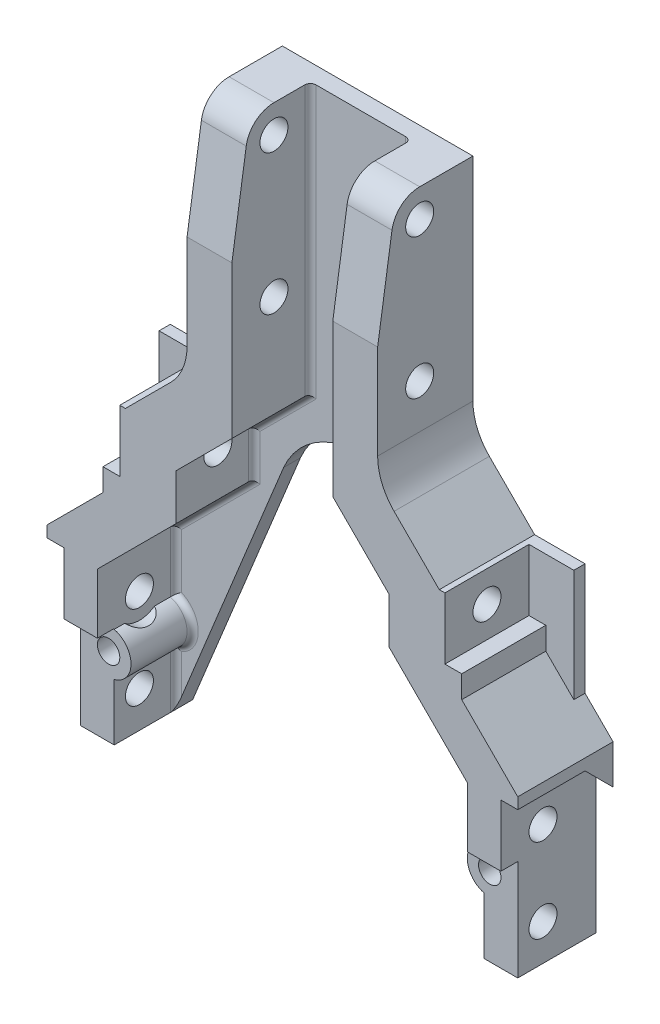
SolidWorks part; units mm, degrees
material "ABS"
ref_plane "Front Plane" through (0, 0, 0) normal (0, 0, 1) x (1, 0, 0)
ref_plane "Top Plane" through (0, 0, 0) normal (0, 1, 0) x (1, 0, 0)
ref_plane "Right Plane" through (0, 0, 0) normal (1, 0, 0) x (0, 0, -1)
sketch "Sketch1" plane through (0, 0, 0) normal (0, 0, 1) x (1, 0, 0)
  line L0 (17, 54.5) -> (17, 12.5)
  line L1 (28, 1.5) -> (17, 12.5)
  line L2 (42, -25.5) -> (39, -25.5)
  line L3 (-42, -25.5) -> (-39, -25.5)
  line L7 (39, -54.5) -> (33, -54.5)
  line L9 (17, 54.5) -> (9, 54.5)
  line L12 (13.7781, -7.5139) -> (33, -54.5)
  line L18 (42, -23.5) -> (37, -18.5)
  line L19 (42, -25.5) -> (42, -23.5)
  line L29 (0, 54.5) -> (9, 54.5)
  line L33 (28, 1.5) -> (29, 1.5)
  line L35 (39, -25.5) -> (39, -54.5)
  line L38 (37, 1.5) -> (37, -18.5)
  line L39 (29, 1.5) -> (37, 1.5)
  line L46 (-28, 1.5) -> (-17, 12.5)
  line L48 (-17, 54.5) -> (-17, 12.5)
  line L53 (-17, 54.5) -> (-9, 54.5)
  line L56 (-42, -23.5) -> (-37, -18.5)
  line L58 (-39, -25.5) -> (-39, -54.5)
  line L63 (-37, 1.5) -> (-37, -18.5)
  line L66 (-28, 1.5) -> (-29, 1.5)
  line L69 (-13.7781, -7.5139) -> (-33, -54.5)
  line L75 (-29, 1.5) -> (-37, 1.5)
  line L76 (-39, -54.5) -> (-33, -54.5)
  line L77 (-42, -25.5) -> (-42, -23.5)
  line L78 (0, 54.5) -> (-9, 54.5)
  arc A0 (13.7781, -7.5139) -> (0, 1.5563) centre (0, -13.4437) ccw
  arc A3 (0, 1.5563) -> (-13.7781, -7.5139) centre (0, -13.4437) ccw
extrude "Boss-Extrude1" add sketch "Sketch1" along normal blind 3
sketch "Sketch2" plane through (0, 0, 3) normal (0, 0, 1) x (1, 0, 0)
  line L0 (-17, 54.5) -> (17, 54.5) construction
  line L1 (17, 54.5) -> (17, 12.5)
  line L2 (28, 1.5) -> (17, 12.5)
  line L3 (33, -30.4706) -> (33, -36.627)
  line L8 (39, -54.5) -> (33, -54.5)
  line L9 (32, -9.5) -> (32, -13.5)
  line L10 (17, 54.5) -> (9, 54.5)
  line L16 (19.0015, -3.6436) -> (9, 6.3579)
  line L17 (9, 54.5) -> (9, 6.3579)
  line L18 (33, -25.8137) -> (19, -11.8137)
  line L19 (42, -23.5) -> (32, -13.5)
  line L20 (42, -25.5) -> (42, -23.5)
  line L22 (33, -30.4706) -> (33, -25.8137)
  line L27 (19, -3.6421) -> (19, -11.8137)
  line L28 (29, -9.5) -> (32, -9.5)
  line L29 (39, -25.5) -> (42, -25.5)
  line L32 (33, -44.373) -> (33, -54.5)
  line L33 (29, -9.5) -> (29, 1.5)
  line L34 (28, 1.5) -> (29, 1.5)
  line L35 (32, -9.5) -> (32, -13.5)
  line L36 (39, -25.5) -> (39, -54.5)
  line L45 (-19.0015, -3.6436) -> (-19.0015, -1.5) construction
  line L47 (-28, 1.5) -> (-17, 12.5)
  line L49 (-17, 54.5) -> (-17, 12.5)
  line L50 (-19, -3.6421) -> (-19, -11.8137)
  line L52 (-19.0015, -1.5) -> (-19.0006, -1.5) construction
  line L53 (-33, -30.4706) -> (-33, -36.627)
  line L54 (-17, 54.5) -> (-9, 54.5)
  line L57 (-42, -23.5) -> (-32, -13.5)
  line L59 (-39, -25.5) -> (-39, -54.5)
  line L60 (-33, -25.8137) -> (-19, -11.8137)
  line L61 (-9, 54.5) -> (-9, 6.3579)
  line L63 (-29, -9.5) -> (-32, -9.5)
  line L66 (-32, -9.5) -> (-32, -13.5)
  line L67 (-28, 1.5) -> (-29, 1.5)
  line L69 (-19.0015, -3.6436) -> (-9, 6.3579)
  line L71 (-29, -9.5) -> (-29, 1.5)
  line L73 (-33, -44.373) -> (-33, -54.5)
  line L74 (-32, -9.5) -> (-32, -13.5)
  line L75 (-39, -25.5) -> (-42, -25.5)
  line L77 (-39, -54.5) -> (-33, -54.5)
  line L78 (-42, -25.5) -> (-42, -23.5)
  line L80 (-33, -30.4706) -> (-33, -25.8137)
  circle A1 centre (34, -40.5) radius 2
  arc A2 (33, -36.627) -> (33, -44.373) centre (34, -40.5) ccw
  circle A4 centre (-34, -40.5) radius 2
  arc A5 (-33, -44.373) -> (-33, -36.627) centre (-34, -40.5) ccw
  line M3 (33, -54.5) -> (39, -54.5)
  line M4 (39, -54.5) -> (39, -25.5)
  line M7 (42, -23.5) -> (37, -18.5)
  line M9 (37, 1.5) -> (28, 1.5)
  line M10 (28, 1.5) -> (17, 12.5)
  line M11 (17, 12.5) -> (17, 54.5)
  line M12 (17, 54.5) -> (-17, 54.5)
  line M13 (-17, 54.5) -> (-17, 12.5)
  line M14 (-17, 12.5) -> (-28, 1.5)
  line M15 (-28, 1.5) -> (-37, 1.5)
  line M17 (-37, -18.5) -> (-42, -23.5)
  line M18 (-42, -23.5) -> (-42, -25.5)
  line M20 (-39, -25.5) -> (-39, -54.5)
  line M21 (-39, -54.5) -> (-33, -54.5)
extrude "Boss-Extrude2" add sketch "Sketch2" along normal blind 14 contours L73 A5 L53 L80 L60 L50 L69 L61 L71 L63 L66 L57 L75 L59 A4 M12 M13 M14 M15 M17 M18 M20 M21 | L3 A2 L32 L36 L29 L19 L9 L28 L33 L17 L16 L27 L18 L22 A1 M3 M4 M7 M9 M10 M11 M12 region at (-22.4143, 1.437, 3) region at (22.4143, 1.437, 3)
sketch "Szkic1" plane through (39, 0, 0) normal (1, 0, 0) x (0, 0, -1)
  line L0 (-17, -54.5) -> (-17, -25.5) construction
  line L1 (-17, -54.5) -> (0, -54.5) construction
  line L2 (-17, -54.5) -> (-14, -54.5)
  line L3 (-17, -54.5) -> (-17, -36.5)
  line L4 (-17, -36.5) -> (-14, -36.5)
  line L5 (-14, -54.5) -> (-14, -36.5)
  line L6 (-17, 33.5) -> (-14.4428, 50.2544)
  line L7 (-17, 12.5) -> (-17, 54.5) construction
  line L9 (-9.5, 54.5) -> (-17, 54.5)
  line L10 (-17, 54.5) -> (-17, 33.5)
  circle A0 centre (-9.5, -48) radius 2.5
  circle A1 centre (-9.5, -33) radius 2.5
  circle A2 centre (-9.5, -4) radius 2.5
  circle A3 centre (-9.5, 24.5) radius 2.5
  circle A4 centre (-9.5, 49.5) radius 2.5
  arc A5 (-9.5, 54.5) -> (-14.4428, 50.2544) centre (-9.5, 49.5) ccw
  dimension "D1" = 7.5
  dimension "D5" = 21.5
  dimension "D6" = 50.5
  dimension "D7" = 79
  dimension "D2" = 18
  dimension "D3" = 3
  dimension "D4" = 6.5
  dimension "D8" = 104
extrude "Wytnij-wyciągnięcie1" cut sketch "Szkic1" against normal through all both and the other way through all
sketch "Szkic2" plane through (-19, 0, 0) normal (1, 0, 0) x (0, 0, -1)
  circle A0 centre (-9.5, -4) radius 5.5
extrude "Wytnij-wyciągnięcie2" cut sketch "Szkic2" along normal up to surface (38 mm away) up to face at (19, -6.8423, 9.8333)
sketch "Szkic3" plane through (-33, 0, 0) normal (1, 0, 0) x (0, 0, -1)
  circle A0 centre (-9.5, -48) radius 4.5
  circle A1 centre (-9.5, -33) radius 4.5
extrude "Wytnij-wyciągnięcie3" cut sketch "Szkic3" along normal up to surface (66 mm away) up to face at (33, -48, 7)
sketch "Szkic4" plane through (39, 0, 0) normal (1, 0, 0) x (0, 0, -1)
  line L0 (-5, -25.5) -> (0, -25.5)
  line L1 (-17, -25.5) -> (0, -25.5) construction
  line L2 (0, -25.5) -> (0, -30.5)
  line L3 (0, -54.5) -> (0, -25.5) construction
  line L4 (0, -30.5) -> (-5, -25.5)
  dimension "D1" = 5
  dimension "D2" = 5
extrude "Dodanie-wyciągnięcie1" add sketch "Szkic4" along normal up to surface (3 mm away) up to face at (42, -24.5, 8.5)
sketch "Szkic5" plane through (-39, 0, 0) normal (-1, 0, 0) x (0, 0, 1)
  line L0 (0, -25.5) -> (0, -30.5)
  line L1 (0, -25.5) -> (0, -54.5) construction
  line L2 (0, -30.5) -> (5, -25.5)
  line L3 (17, -25.5) -> (0, -25.5) construction
  line L4 (5, -25.5) -> (0, -25.5)
  dimension "D1" = 5
  dimension "D2" = 5
extrude "Dodanie-wyciągnięcie2" add sketch "Szkic5" along normal up to surface (3 mm away) up to face at (-42, -24.5, 8.5)
fillet "Zaokrąglenie2" radius 1 14 edges at (-9, 30.4289, 3) (-14, 1.3579, 3) (-19, -7.7279, 3) (-26, -18.8137, 3) (-33, -31.2204, 3) (-30, -40.5, 3) (-33, -49.4365, 3) (9, 30.4289, 3) (14, 1.3579, 3) (19, -7.7279, 3) (26, -18.8137, 3) (33, -31.2204, 3) (30, -40.5, 3) (33, -49.4365, 3)
sketch "Szkic6" plane through (0, 0, 3) normal (0, 0, 1) x (1, 0, 0)
  line L0 (29, 1.5) -> (37, 1.5)
  line L1 (37, 1.5) -> (37, -18.5)
  line L2 (37, -18.5) -> (32, -13.5)
  line L3 (32, -13.5) -> (32, -9.5)
  line L4 (32, -9.5) -> (29, -9.5)
  line L5 (29, -9.5) -> (29, 1.5)
  line L6 (-37, 1.5) -> (-29, 1.5)
  line L7 (-29, 1.5) -> (-29, -9.5)
  line L8 (-29, -9.5) -> (-32, -9.5)
  line L9 (-32, -9.5) -> (-32, -13.5)
  line L10 (-32, -13.5) -> (-37, -18.5)
  line L11 (-42, -23.5) -> (-32, -13.5) construction
  line L12 (-37, -18.5) -> (-37, 1.5)
extrude "Wytnij-wyciągnięcie4" cut sketch "Szkic6" against normal blind 1
fillet "Zaokrąglenie3" radius 10 2 edges at (-17, 12.5, 8.5) (17, 12.5, 8.5)
